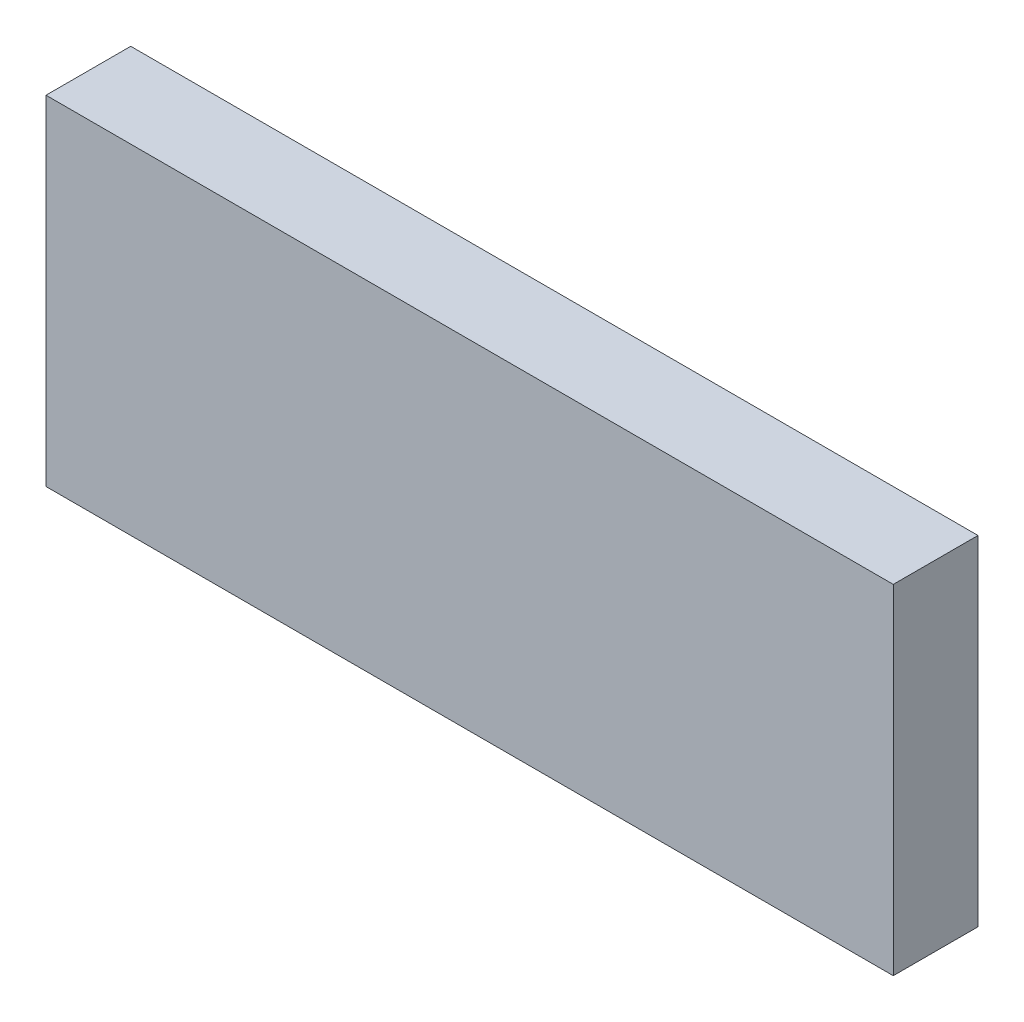
SolidWorks part; units mm, degrees
ref_plane "Front Plane" through (0, 0, 0) normal (0, 0, 1) x (1, 0, 0)
ref_plane "Top Plane" through (0, 0, 0) normal (0, 1, 0) x (1, 0, 0)
ref_plane "Right Plane" through (0, 0, 0) normal (1, 0, 0) x (0, 0, -1)
other "Configuration Table"
sketch "Sketch1" plane through (0, 0, 0) normal (0, 0, 1) x (1, 0, 0)
  line L1 (0, 0) -> (254, 0)
  line L2 (0, 0) -> (0, 101.6)
  line L3 (0, 101.6) -> (254, 101.6)
  line L4 (254, 0) -> (254, 101.6)
sheet metal parameters "Sheet-Metal1" thickness 25.4 parameters "D1"=0.7366
base flange "Base-Flange1" sketch "Sketch1" thickness 25.4 reverse thickness direction yes parameters "D1"=0.7366
flat pattern "Flat-Pattern1" [suppressed]
sketch "Bend-Lines1" plane through (0, 0, 0) normal (0, 1, 0) x (-1, 0, 0)
